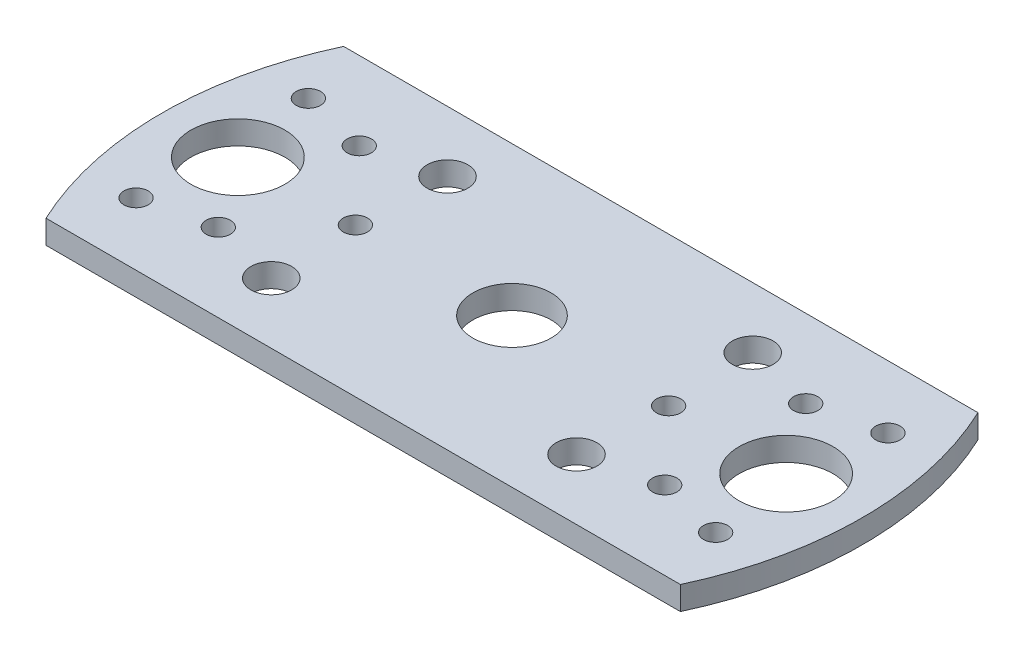
SolidWorks part; units mm, degrees
material "Thornel Mat VMA"
ref_plane "Front Plane" through (0, 0, 0) normal (0, 0, 1) x (1, 0, 0)
ref_plane "Top Plane" through (0, 0, 0) normal (0, 1, 0) x (1, 0, 0)
ref_plane "Right Plane" through (0, 0, 0) normal (1, 0, 0) x (0, 0, -1)
sketch "Sketch1" plane through (0, 0, 0) normal (0, 1, 0) x (1, 0, 0)
  line L0 (0, 0) -> (0, 56.5511) construction
  line L1 (0, 0) -> (118.6796, 0) construction
  line L2 (-62, 19) -> (62, 19)
  line L5 (-62, -19) -> (62, -19)
  line L6 (62, 19) -> (62, 13)
  line L7 (62, 13) -> (59, 13)
  line L8 (59, 13) -> (59, -13)
  line L9 (62, -13) -> (59, -13)
  line L10 (62, -19) -> (62, -13)
  line L11 (-62, -19) -> (-62, -13)
  line L12 (-62, -13) -> (-59, -13)
  line L13 (-59, 13) -> (-59, -13)
  line L14 (-62, 13) -> (-59, 13)
  line L15 (-62, 19) -> (-62, 13)
  circle A0 centre (37, 11) radius 1.55
  circle A1 centre (-37, 11) radius 1.55
  circle A2 centre (-37, -11) radius 1.55
  circle A3 centre (37, -11) radius 1.55
  circle A4 centre (0, 0) radius 5
  circle A5 centre (20, 0) radius 1.55
  circle A6 centre (-20, 0) radius 1.55
  circle A7 centre (35, 0) radius 6
  circle A8 centre (-35, 0) radius 6
  circle A9 centre (28.5, 9) radius 1.55
  circle A10 centre (28.5, -9) radius 1.55
  circle A11 centre (-28.5, -9) radius 1.55
  circle A12 centre (-28.5, 9) radius 1.55
  point P13 (0, 19)
  point P18 (-61, 0)
  point P19 (61, 0)
  point P28 (59, 0)
  dimension "D1" = 3.1
  dimension "D2" = 22
  dimension "D3" = 8
  dimension "D4" = 3.1
  dimension "D5" = 10
  dimension "D6" = 20
  dimension "D11" = 35
  dimension "D12" = 12
  dimension "D13" = 8.5
  dimension "D14" = 2
  dimension "D7" = 38
  dimension "D8" = 124
  dimension "D9" = 3
  dimension "D10" = 6
extrude "Boss-Extrude1" add sketch "Sketch1" along normal blind 3
fillet "Fillet1" radius 3 8 edges at (-62, 1.5, -19) (-62, 1.5, -13) (-62, 1.5, 13) (-62, 1.5, 19) (62, 1.5, 19) (62, 1.5, 13) (62, 1.5, -13) (62, 1.5, -19)
sketch "草图2" plane through (0, 3, 0) normal (0, 1, 0) x (1, 0, 0)
  line L0 (0, 19) -> (0, -19) construction
  line L1 (59, 19) -> (-59, 19) construction
  line L2 (-59, -19) -> (59, -19) construction
  line L3 (0, 0) -> (-21.55, 0) construction
  circle A0 centre (-20, 0) radius 1.55 construction
sketch "草图3" plane through (0, 0, 0) normal (0, -1, 0) x (1, 0, 0)
  circle A0 centre (-30.75, -15) radius 2.1 construction
  circle A1 centre (-30.75, -15) radius 2.1
  circle A2 centre (-30.75, 15) radius 2.1 construction
  circle A3 centre (-30.75, 15) radius 2.1
sketch "草图4" plane through (0, 0, 0) normal (0, -1, 0) x (1, 0, 0)
  line L0 (0, 0) -> (0, 63.4958) construction
  line L1 (-45, 19) -> (-45, -19)
  line L2 (-59, 19) -> (59, 19) construction
  line L3 (59, -19) -> (-59, -19) construction
  line L4 (-45, -19) -> (-67.4332, -19)
  line L5 (-67.4332, -19) -> (-67.4332, 19)
  line L6 (-67.4332, 19) -> (-45, 19)
  line L7 (67.4332, 19) -> (45, 19)
  line L8 (67.4332, -19) -> (67.4332, 19)
  line L9 (45, -19) -> (67.4332, -19)
  line L10 (45, 19) -> (45, -19)
  dimension "D1" = 45
extrude "切除-拉伸1" cut sketch "草图4" against normal blind 10
sketch "草图6" plane through (0, 3, 0) normal (0, 1, 0) x (1, 0, 0)
  line L1 (45, 19) -> (-45, 19) construction
  line L2 (-45, -19) -> (45, -19) construction
  line L3 (-40.5, -19) -> (-45, -19)
  line L4 (-45, -19) -> (-45, 19)
  line L5 (-45, 19) -> (-40.5, 19)
  line L6 (0, 0) -> (0, 31.3174) construction
  line L7 (45, 19) -> (40.5, 19)
  line L8 (45, -19) -> (45, 19)
  line L9 (40.5, -19) -> (45, -19)
  circle A0 centre (0, 0) radius 44.7353 construction
  arc A1 (-40.5, 19) -> (-40.5, -19) centre (0, 0) ccw
  arc A2 (40.5, 19) -> (40.5, -19) centre (0, 0) cw
extrude "切除-拉伸2" cut sketch "草图6" against normal blind 10
sketch "草图7" plane through (0, 0, 0) normal (0, -1, 0) x (1, 0, 0)
  line L0 (0, 0) -> (0, -31.3174) construction
  circle A0 centre (0, -22.5) radius 2.6
  circle A1 centre (-19.4856, -11.25) radius 2.6
  circle A2 centre (-19.4856, 11.25) radius 2.6
  circle A3 centre (0, 22.5) radius 2.6
  circle A4 centre (19.4856, 11.25) radius 2.6
  circle A5 centre (19.4856, -11.25) radius 2.6
  point P18 (0, 0)
  dimension "D3" = 5.2
  dimension "D1" = 22.5
  dimension "D2" = 6
extrude "切除-拉伸3" cut sketch "草图7" against normal blind 10
